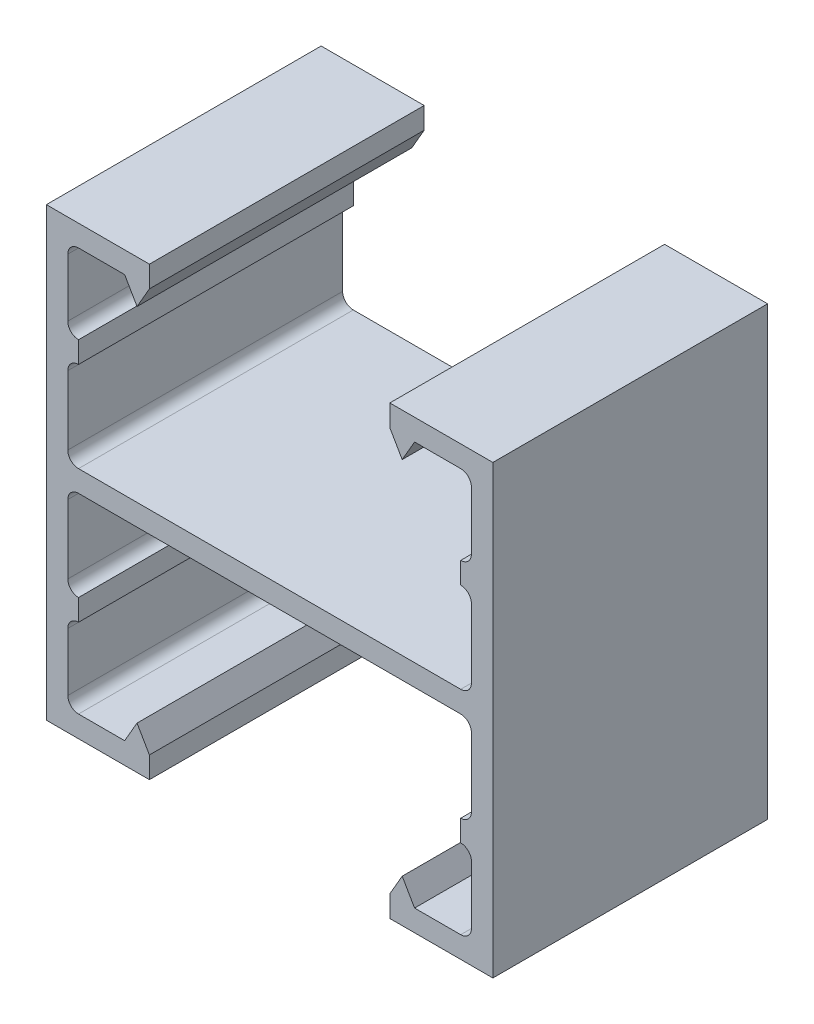
SolidWorks part; units mm, degrees
ref_plane "Plane1" through (0, 0, 0) normal (0, 0, 1) x (1, 0, 0)
ref_plane "Plane2" through (0, 0, 0) normal (0, 1, 0) x (1, 0, 0)
ref_plane "Plane3" through (0, 0, 0) normal (1, 0, 0) x (0, 0, -1)
sketch "Sketch1" plane through (0, 0, 0) normal (0, 0, 1) x (1, 0, 0)
  line L0 (-11.1125, 20.6375) -> (-20.6375, 20.6375)
  line L1 (-20.6375, 20.6375) -> (-20.6375, -20.6375)
  line L2 (-13.4002, -18.6563) -> (-17.6657, -18.6563)
  line L3 (20.6375, -20.6375) -> (20.6375, 20.6375)
  line L4 (20.6375, 20.6375) -> (11.1125, 20.6375)
  line L5 (17.6657, 18.6563) -> (13.4002, 18.6563)
  line L6 (18.6563, 1.9812) -> (18.6563, 9.3282)
  line L7 (-17.6657, 0.9906) -> (17.6657, 0.9906)
  line L8 (-18.6563, 17.6657) -> (-18.6563, 11.3093)
  line L9 (-13.4002, 18.6563) -> (-17.6657, 18.6563)
  line L10 (13.4002, 18.6563) -> (12.2563, 16.6751)
  line L11 (12.2563, 16.6751) -> (11.1125, 18.6563)
  line L12 (11.1125, 18.6563) -> (11.1125, 20.6375)
  line L13 (-13.4002, 18.6563) -> (-12.2563, 16.6751)
  line L14 (-12.2563, 16.6751) -> (-11.1125, 18.6563)
  line L15 (-11.1125, 18.6563) -> (-11.1125, 20.6375)
  line L16 (22.86, 0) -> (-25.4, 0) construction
  line L17 (12.2563, -16.6751) -> (11.1125, -18.6563)
  line L18 (13.4002, -18.6563) -> (12.2563, -16.6751)
  line L19 (17.6657, -18.6563) -> (13.4002, -18.6563)
  line L20 (20.6375, -20.6375) -> (11.1125, -20.6375)
  line L21 (11.1125, -18.6563) -> (11.1125, -20.6375)
  line L22 (-11.1125, -20.6375) -> (-20.6375, -20.6375)
  line L23 (-11.1125, -18.6563) -> (-11.1125, -20.6375)
  line L24 (-12.2563, -16.6751) -> (-11.1125, -18.6563)
  line L25 (-13.4002, -18.6563) -> (-12.2563, -16.6751)
  line L26 (-18.6563, -17.6657) -> (-18.6563, -11.3094)
  line L27 (18.6563, -1.9812) -> (18.6563, -9.3281)
  line L28 (-17.6657, -0.9906) -> (17.6657, -0.9906)
  line L29 (-18.6563, 11.3093) -> (-17.6657, 11.3093)
  line L30 (-17.6657, 11.3093) -> (-17.6657, 9.3281)
  line L31 (-17.6657, 9.3281) -> (-18.6563, 9.3281)
  line L32 (-18.6563, 9.3281) -> (-18.6563, 1.9812)
  line L33 (18.6563, 11.3093) -> (17.6657, 11.3094)
  line L34 (17.6657, 11.3094) -> (17.6657, 9.3282)
  line L35 (17.6657, 9.3282) -> (18.6563, 9.3282)
  line L36 (18.6563, 11.3093) -> (18.6563, 17.6657)
  line L37 (17.6657, -9.3281) -> (18.6563, -9.3281)
  line L38 (17.6657, -11.3093) -> (17.6657, -9.3281)
  line L39 (18.6563, -11.3093) -> (17.6657, -11.3093)
  line L40 (-17.6657, -9.3281) -> (-18.6563, -9.3281)
  line L41 (-17.6657, -11.3093) -> (-17.6657, -9.3281)
  line L42 (-18.6563, -11.3094) -> (-17.6657, -11.3093)
  line L43 (18.6563, -11.3093) -> (18.6563, -17.6657)
  line L44 (-18.6563, -9.3281) -> (-18.6563, -1.9812)
  arc A0 (-18.6563, 1.9812) -> (-17.6657, 0.9906) centre (-17.6657, 1.9812) ccw
  arc A1 (-17.6657, 18.6563) -> (-18.6563, 17.6657) centre (-17.6657, 17.6657) ccw
  arc A2 (18.6563, 17.6657) -> (17.6657, 18.6563) centre (17.6657, 17.6657) ccw
  arc A3 (17.6657, 0.9906) -> (18.6563, 1.9812) centre (17.6657, 1.9812) ccw
  arc A4 (18.6563, -17.6657) -> (17.6657, -18.6563) centre (17.6657, -17.6657) cw
  arc A5 (-17.6657, -18.6563) -> (-18.6563, -17.6657) centre (-17.6657, -17.6657) cw
  arc A6 (17.6657, -0.9906) -> (18.6563, -1.9812) centre (17.6657, -1.9812) cw
  arc A7 (-18.6563, -1.9812) -> (-17.6657, -0.9906) centre (-17.6657, -1.9812) cw
  dimension "D8" = 20.6375
  dimension "D10" = 22.225
  dimension "D13" = 1.1438
  dimension "Height" = 41.275
  dimension "D3" = 20.6375
  dimension "D1" = 0.9906
  dimension "D6" = 11.3093
  dimension "D4" = 60
extrude "Base-Extrude" add sketch "Sketch1" along normal mid plane 25.4
fillet "Fillet1" radius 0.9906 8 edges at (18.6563, 11.3093, 0) (18.6563, -9.3281, 0) (-18.6563, 11.3093, 0) (-18.6563, -9.3281, 0) (-18.6563, 9.3281, 0) (-18.6563, -11.3094, 0) (18.6563, 9.3282, 0) (18.6563, -11.3093, 0)
equation "\"D8@Sketch1\" = \"Width@Sketch1\" / 2"
equation "\"D10@Sketch1\" = \"Width@Sketch1\" - 2 * \"edge@Sketch1\""
equation "\"D5@Sketch1\" = \"gauge@Sketch1\" / 2"
equation "\"D3@Sketch1\" = \"Height@Sketch1\" / 2"
equation "\"D1@Sketch1\" = \"D5@Sketch1\""
equation "\"D6@Sketch1\" = \"D3@Sketch1\" / 2 + \"D5@Sketch1\""
equation "\"D1@Fillet1\" = \"D5@Sketch1\""
equation "\"D13@Sketch1\" = \"gauge@Sketch1\" * .577350269"
